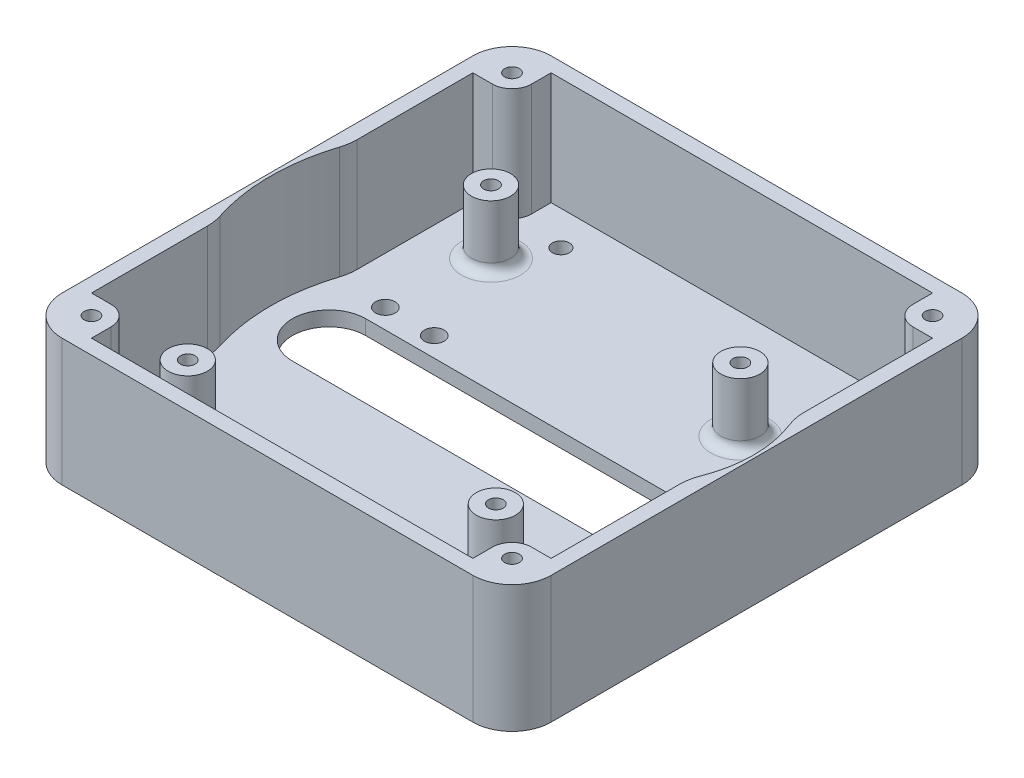
SolidWorks part; units mm, degrees
ref_plane "Спереди" through (0, 0, 0) normal (0, 0, 1) x (1, 0, 0)
ref_plane "Сверху" through (0, 0, 0) normal (0, 1, 0) x (1, 0, 0)
ref_plane "Справа" through (0, 0, 0) normal (1, 0, 0) x (0, 0, -1)
sketch "Эскиз1" plane through (0, 0, 0) normal (0, 1, 0) x (1, 0, 0)
  line L0 (0, 50) -> (100, 50) construction
  line L17 (0, 0) -> (100, 0)
  line L18 (0, 0) -> (0, 100)
  line L19 (0, 100) -> (100, 100)
  line L20 (100, 0) -> (100, 100)
  line L21 (50, 100) -> (50, 0) construction
  circle A0 centre (14.7, 81) radius 1.5
  circle A1 centre (71.7, 75) radius 1.5
  circle A2 centre (71.7, 25) radius 1.5
  circle A3 centre (14.7, 19) radius 1.5
  circle A5 centre (7, 93) radius 1.5
  circle A6 centre (93, 93) radius 1.5
  circle A7 centre (93, 7) radius 1.5
  circle A8 centre (7, 7) radius 1.5
  dimension "D3" = 3
  dimension "D8" = 3
  dimension "D1" = 100
  dimension "D2" = 100
  dimension "D4" = 62
  dimension "D5" = 50
  dimension "D6" = 57
  dimension "D7" = 28.3
  dimension "D9" = 7
  dimension "D10" = 7
extrude "Бобышка-Вытянуть1" add sketch "Эскиз1" along normal blind 3
sketch "Эскиз4" plane through (0, 3, 0) normal (0, 1, 0) x (1, 0, 0)
  line L0 (97, 97) -> (3, 97)
  line L1 (3, 97) -> (3, 65.3049)
  line L2 (3, 3) -> (97, 3)
  line L3 (97, 3) -> (97, 37.2627)
  line L4 (0, 100) -> (0, 0)
  line L5 (0, 0) -> (100, 0)
  line L6 (100, 0) -> (100, 100)
  line L7 (100, 100) -> (0, 100)
  line L8 (0, 100) -> (0, 0)
  line L9 (0, 0) -> (100, 0)
  line L10 (100, 0) -> (100, 100)
  line L11 (100, 100) -> (0, 100)
  line L12 (0, 50) -> (100, 50) construction
  line L13 (3, 34.6951) -> (3, 3)
  line L14 (3, 97) -> (3, 3) construction
  line L15 (97, 62.7373) -> (97, 97)
  line L16 (97, 3) -> (97, 97) construction
  arc A0 (2.52, 62.2439) -> (2.52, 37.7561) centre (40.6, 50) ccw
  arc A1 (97.6857, 40.9019) -> (97.6857, 59.0981) centre (74.4, 50) ccw
  arc A2 (97.6857, 59.0981) -> (97, 62.7373) centre (107, 62.7373) cw
  arc A3 (97.6857, 40.9019) -> (97, 37.2627) centre (107, 37.2627) ccw
  arc A4 (2.52, 37.7561) -> (3, 34.6951) centre (-7, 34.6951) cw
  arc A5 (2.52, 62.2439) -> (3, 65.3049) centre (-7, 65.3049) ccw
  point P12 (0.6, 50)
  point P16 (99.4, 50)
  point P20 (97, 60.6883)
  point P25 (3, 36.353)
  dimension "D4" = 80
  dimension "D6" = 50
  dimension "D7" = 10
  dimension "D3" = 0.6
  dimension "D5" = 0.6
  dimension "D1" = 0
  dimension "D2" = 3
extrude "Бобышка-Вытянуть4" add sketch "Эскиз4" along normal blind 23
sketch "Эскиз5" plane through (0, 3, 0) normal (0, 1, 0) x (1, 0, 0)
  circle A0 centre (14.7, 81) radius 4
  circle A1 centre (14.7, 81) radius 1.5 construction
  circle A2 centre (14.7, 81) radius 1.5
  circle A3 centre (14.7, 19) radius 1.5 construction
  circle A4 centre (71.7, 25) radius 1.5 construction
  circle A5 centre (71.7, 75) radius 1.5 construction
  circle A6 centre (14.7, 19) radius 1.5
  circle A7 centre (71.7, 25) radius 1.5
  circle A8 centre (71.7, 75) radius 1.5
  circle A9 centre (71.7, 75) radius 4
  circle A10 centre (71.7, 25) radius 4
  circle A11 centre (14.7, 19) radius 4
  dimension "D1" = 8
extrude "Бобышка-Вытянуть5" add sketch "Эскиз5" along normal blind 13
fillet "Скругление2" radius 2 4 edges at (14.7, 3, -23) (71.7, 3, -29) (71.7, 3, -79) (14.7, 3, -85)
fillet "Скругление3" radius 8 4 edges at (100, 13, -100) (100, 13, 0) (0, 13, 0) (0, 13, -100)
sketch "Эскиз7" plane through (0, 3, 0) normal (0, 1, 0) x (1, 0, 0)
  line L0 (3, 97) -> (3, 65.3049) construction
  line L2 (97, 97) -> (3, 97) construction
  line L6 (50, 97) -> (50, 3) construction
  line L7 (3, 3) -> (97, 3) construction
  line L8 (0, 50) -> (100, 50) construction
  line L9 (0, 92) -> (0, 8) construction
  line L10 (100, 8) -> (100, 92) construction
  line L15 (3, 89) -> (3, 97)
  line L16 (3, 97) -> (11, 97)
  line L17 (7, 89) -> (3, 89)
  line L18 (3, 97) -> (3, 65.3049) construction
  line L19 (11, 93) -> (11, 97)
  line L20 (97, 97) -> (3, 97) construction
  line L21 (89, 93) -> (89, 97)
  line L22 (93, 89) -> (97, 89)
  line L23 (97, 97) -> (89, 97)
  line L24 (97, 89) -> (97, 97)
  line L25 (97, 11) -> (97, 3)
  line L26 (97, 3) -> (89, 3)
  line L27 (93, 11) -> (97, 11)
  line L28 (89, 7) -> (89, 3)
  line L29 (11, 7) -> (11, 3)
  line L30 (7, 11) -> (3, 11)
  line L31 (3, 3) -> (11, 3)
  line L32 (3, 11) -> (3, 3)
  arc A0 (7, 89) -> (11, 93) centre (7, 93) ccw
  circle A17 centre (7, 93) radius 1.5 construction
  circle A18 centre (7, 93) radius 1.5
  circle A19 centre (93, 93) radius 1.5
  arc A20 (93, 89) -> (89, 93) centre (93, 93) cw
  arc A21 (93, 11) -> (89, 7) centre (93, 7) ccw
  circle A22 centre (93, 7) radius 1.5
  circle A23 centre (7, 7) radius 1.5
  arc A24 (7, 11) -> (11, 7) centre (7, 7) cw
extrude "Бобышка-Вытянуть6" add sketch "Эскиз7" along normal up to surface (23 mm away) up to face at (50, 26, -50)
sketch "Эскиз8" plane through (0, 3, 0) normal (0, 1, 0) x (1, 0, 0)
  line L0 (0, 50) -> (100, 50) construction
  line L1 (0, 92) -> (0, 8) construction
  line L2 (100, 8) -> (100, 92) construction
  line L3 (50, 100) -> (50, 0) construction
  line L4 (92, 100) -> (8, 100) construction
  line L5 (8, 0) -> (92, 0) construction
  line L6 (12.5921, 50) -> (87.5921, 50) construction
  line L7 (12.5921, 57.5) -> (87.5921, 57.5)
  line L8 (12.5921, 42.5) -> (87.5921, 42.5)
  arc A0 (12.5921, 57.5) -> (12.5921, 42.5) centre (12.5921, 50) ccw
  arc A1 (87.5921, 42.5) -> (87.5921, 57.5) centre (87.5921, 50) ccw
  circle A2 centre (20, 90) radius 1.75
  circle A3 centre (80, 90) radius 1.75
  circle A4 centre (80, 10) radius 1.75
  circle A5 centre (20, 10) radius 1.75
  circle A6 centre (22.5921, 61.5084) radius 2
  circle A7 centre (12.5921, 61.5084) radius 2
  point P14 (50.0921, 50)
  point P31 (12.5921, 61.5084)
  dimension "D3" = 3.5
  dimension "D6" = 4
  dimension "D1" = 15
  dimension "D2" = 75
  dimension "D4" = 60
  dimension "D5" = 80
  dimension "D7" = 10
extrude "Вырез-Вытянуть2" cut sketch "Эскиз8" against normal up to surface (3 mm away) up to face at (93, 0, -5.5)
